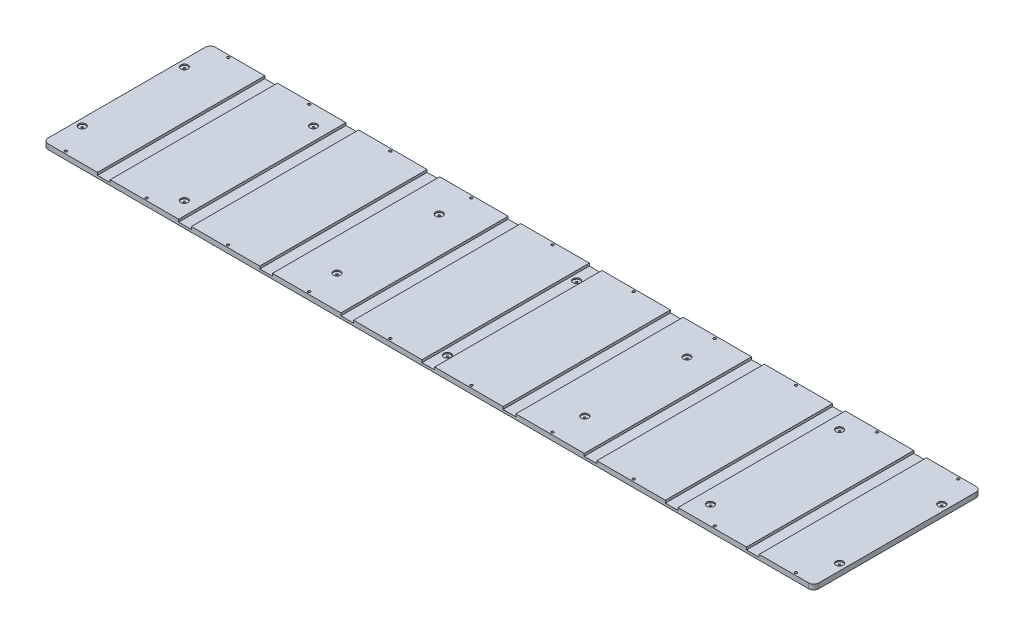
SolidWorks part; units mm, degrees
material "PE High Density"
ref_plane "Front Plane" through (0, 0, 0) normal (0, 0, 1) x (1, 0, 0)
ref_plane "Top Plane" through (0, 0, 0) normal (0, 1, 0) x (1, 0, 0)
ref_plane "Right Plane" through (0, 0, 0) normal (1, 0, 0) x (0, 0, -1)
sketch "Sketch1" plane through (0, 0, 0) normal (0, 1, 0) x (1, 0, 0)
  line L1 (0, 0) -> (1930.4, 0)
  line L2 (0, 0) -> (0, 419.1)
  line L3 (0, 419.1) -> (1930.4, 419.1)
  line L4 (1930.4, 0) -> (1930.4, 419.1)
  dimension "D1" = 1930.4
  dimension "D2" = 419.1
extrude "Boss-Extrude1" add sketch "Sketch1" along normal blind 12.7
sketch "Sketch2" plane through (0, 12.7, 0) normal (0, 1, 0) x (1, 0, 0)
  line L0 (1930.4, 419.1) -> (0, 419.1) construction
  line L2 (0, 419.1) -> (0, 0) construction
  line L3 (965.2, 419.1) -> (965.2, 0) construction
  line L4 (0, 0) -> (1930.4, 0) construction
  circle A0 centre (16.6688, 337.566) radius 2.4511
  circle A1 centre (654.8438, 337.566) radius 2.4511
  circle A2 centre (654.8438, 81.534) radius 2.4511
  circle A3 centre (16.6688, 81.534) radius 2.4511
  circle A4 centre (1275.5562, 337.566) radius 2.4511
  circle A5 centre (1275.5563, 81.534) radius 2.4511
  circle A6 centre (1913.7312, 337.566) radius 2.4511
  circle A7 centre (1913.7312, 81.534) radius 2.4511
  point P0 (16.6688, 337.566)
  point P5 (654.8438, 337.566)
  point P10 (654.8438, 81.534)
  point P17 (16.6688, 81.534)
  point P20 (1293.0187, 337.566)
  point P21 (1293.0187, 81.534)
  point P22 (1931.1937, 81.534)
  point P23 (1931.1937, 337.566)
  point P24 (1275.5562, 337.566)
  point P25 (1275.5563, 81.534)
  point P26 (1913.7312, 81.534)
  point P27 (1913.7312, 337.566)
  point P44 (0, 209.55)
  dimension "D7" = 4.9022
  dimension "D5" = 16.6687
  dimension "D6" = 256.032
  dimension "D4" = 638.175
  dimension "D1" = 128.016
  dimension "D2" = 4
  dimension "D3" = 2
sketch "Sketch7" plane through (0, 12.7, 0) normal (0, 1, 0) x (1, 0, 0)
  line L0 (0, 419.1) -> (0, 0) construction
  line L1 (0, 371.348) -> (1930.4, 371.348) construction
  line L2 (1930.4, 0) -> (1930.4, 419.1) construction
  circle A0 centre (306.324, 371.348) radius 2.4511
  circle A1 centre (306.324, 47.752) radius 2.4511
  circle A2 centre (965.2, 47.752) radius 2.4511
  circle A3 centre (965.2, 371.348) radius 2.4511
  circle A4 centre (1624.076, 371.348) radius 2.4511
  circle A5 centre (1624.076, 47.752) radius 2.4511
  point P0 (306.324, 371.348)
  point P3 (0, 209.55)
  point P8 (965.2, 371.348)
  point P9 (1624.076, 371.348)
  point P13 (965.2, 47.752)
  point P14 (1624.076, 47.752)
  point P18 (306.324, 47.752)
  dimension "D7" = 4.9022
  dimension "D5" = 658.876
  dimension "D6" = 323.596
  dimension "D2" = 161.798
  dimension "D3" = 3
fillet "Fillet1" radius 12.7 4 edges at (1930.4, 6.35, 0) (1930.4, 6.35, -419.1) (0, 6.35, 0) (0, 6.35, -419.1)
sketch "Sketch8" plane through (0, 12.7, 0) normal (0, 1, 0) x (1, 0, 0)
  line L0 (136.525, 419.1) -> (136.525, 0)
  line L1 (1917.7, 419.1) -> (12.7, 419.1) construction
  line L2 (12.7, 0) -> (1917.7, 0) construction
  line L3 (168.275, 419.1) -> (168.275, 0)
  line L4 (136.525, 419.1) -> (168.275, 419.1)
  line L5 (136.525, 0) -> (168.275, 0)
  line L6 (0, 406.4) -> (0, 12.7) construction
  line L7 (339.725, 0) -> (371.475, 0)
  line L8 (371.475, 419.1) -> (371.475, 0)
  line L9 (339.725, 419.1) -> (371.475, 419.1)
  line L10 (339.725, 419.1) -> (339.725, 0)
  line L11 (542.925, 0) -> (574.675, 0)
  line L12 (574.675, 419.1) -> (574.675, 0)
  line L13 (542.925, 419.1) -> (574.675, 419.1)
  line L14 (542.925, 419.1) -> (542.925, 0)
  line L15 (746.125, 0) -> (777.875, 0)
  line L16 (777.875, 419.1) -> (777.875, 0)
  line L17 (746.125, 419.1) -> (777.875, 419.1)
  line L18 (746.125, 419.1) -> (746.125, 0)
  line L19 (949.325, 0) -> (981.075, 0)
  line L20 (981.075, 419.1) -> (981.075, 0)
  line L21 (949.325, 419.1) -> (981.075, 419.1)
  line L22 (949.325, 419.1) -> (949.325, 0)
  line L23 (1152.525, 0) -> (1184.275, 0)
  line L24 (1184.275, 419.1) -> (1184.275, 0)
  line L25 (1152.525, 419.1) -> (1184.275, 419.1)
  line L26 (1152.525, 419.1) -> (1152.525, 0)
  line L27 (1355.725, 0) -> (1387.475, 0)
  line L28 (1387.475, 419.1) -> (1387.475, 0)
  line L29 (1355.725, 419.1) -> (1387.475, 419.1)
  line L30 (1355.725, 419.1) -> (1355.725, 0)
  line L31 (1558.925, 0) -> (1590.675, 0)
  line L32 (1590.675, 419.1) -> (1590.675, 0)
  line L33 (1558.925, 419.1) -> (1590.675, 419.1)
  line L34 (1558.925, 419.1) -> (1558.925, 0)
  line L35 (1762.125, 0) -> (1793.875, 0)
  line L36 (1793.875, 419.1) -> (1793.875, 0)
  line L37 (1762.125, 419.1) -> (1793.875, 419.1)
  line L38 (1762.125, 419.1) -> (1762.125, 0)
  dimension "D1" = 31.75
  dimension "D2" = 136.525
  dimension "D4" = 203.2
  dimension "D3" = 9
extrude "Cut-Extrude3" cut sketch "Sketch8" against normal blind 6.35
hole_wizard "1/4 (0.25) Diameter Hole1" positions "Sketch9" profile "Sketch10" hole size "1/4" standard "ANSI Inch" end condition through all
sketch "Sketch9" plane through (0, 12.7, 0) normal (0, 1, 0) x (1, 0, 0)
  line L1 (168.275, 0) -> (339.725, 0) construction
  line L2 (168.275, 0) -> (168.275, 419.1) construction
  line L3 (0, 209.55) -> (1930.4, 209.55) construction
  line L4 (0, 406.4) -> (0, 12.7) construction
  line L5 (1930.4, 12.7) -> (1930.4, 406.4) construction
  point P8 (254, 6.35)
  point P33 (457.2, 6.35)
  point P34 (660.4, 6.35)
  point P35 (863.6, 6.35)
  point P36 (1066.8, 6.35)
  point P37 (1270, 6.35)
  point P38 (1473.2, 6.35)
  point P39 (1676.4, 6.35)
  point P40 (254, 6.35)
  point P41 (457.2, 6.35)
  point P42 (660.4, 6.35)
  point P43 (863.6, 6.35)
  point P44 (1066.8, 6.35)
  point P45 (1270, 6.35)
  point P46 (1473.2, 6.35)
  point P47 (50.8, 6.35)
  point P48 (1879.6, 6.35)
  point P49 (1676.4, 6.35)
  point P50 (1676.4, 412.75)
  point P51 (1879.6, 412.75)
  point P52 (50.8, 412.75)
  point P53 (1473.2, 412.75)
  point P54 (1270, 412.75)
  point P55 (1066.8, 412.75)
  point P56 (863.6, 412.75)
  point P57 (660.4, 412.75)
  point P58 (457.2, 412.75)
  point P59 (254, 412.75)
  dimension "D1" = 6.35
  dimension "D2" = 85.725
  dimension "D5" = 203.2
  dimension "D3" = 9
  dimension "D4" = 2
sketch "Sketch10" plane through (254, 12.7, -6.35) normal (1, 0, 0) x (0, 0, 1)
  line L0 (0, 0) -> (0, 12.7)
  line L1 (0, 12.7) -> (3.175, 12.7)
  line L2 (3.175, 12.7) -> (3.175, 0)
  line L5 (3.175, 0) -> (0, 0)
  line L11 (0, -6.35) -> (0, 107.95) construction
  dimension "Thru Hole Dia." = 6.35
  dimension "Thru Hole Depth" = 12.7
hole_wizard "CBORE for #10 Socket Head Cap Screw1" positions "Sketch11" profile "Sketch12" counterbore size "#10" standard "ANSI Inch" end condition through all
sketch "Sketch11" plane through (0, 12.7, 0) normal (0, 1, 0) x (1, 0, 0)
  point P0 (16.6688, 337.566)
  point P3 (16.6688, 81.534)
  point P6 (306.324, 47.752)
  point P9 (306.324, 371.348)
  point P12 (654.8438, 337.566)
  point P15 (654.8438, 81.534)
  point P18 (965.2, 371.348)
  point P21 (965.2, 47.752)
  point P24 (1275.5563, 81.534)
  point P27 (1275.5562, 337.566)
  point P30 (1624.076, 371.348)
  point P33 (1624.076, 47.752)
  point P36 (1913.7312, 81.534)
  point P39 (1913.7312, 337.566)
sketch "Sketch12" plane through (16.6688, 12.7, -337.566) normal (1, 0, 0) x (0, 0, 1)
  line L0 (0, 0) -> (0, 12.7)
  line L1 (0, 12.7) -> (2.4511, 12.7)
  line L3 (2.4511, 12.7) -> (2.4511, 3.175)
  line L4 (2.4511, 3.175) -> (9.0488, 3.175)
  line L5 (9.0488, 3.175) -> (9.0488, 0)
  line L7 (9.0488, 0) -> (0, 0)
  line L11 (0, -6.35) -> (0, 107.95) construction
  dimension "Thru Hole Dia." = 4.9022
  dimension "Thru Hole Depth" = 12.7
  dimension "C'Bore Dia." = 18.0975
  dimension "C'Bore Depth" = 3.175
hole_wizard "CBORE for #10 Binding Head Machine Screw1" positions "Sketch13" profile "Sketch14" counterbore size "#10" standard "ANSI Inch" end condition through all
sketch "Sketch13" plane through (0, 6.35, 0) normal (0, 1, 0) x (1, 0, 0)
  circle A0 centre (965.2, 371.348) radius 2.4511 construction
  circle A1 centre (965.2, 47.752) radius 2.4511 construction
  point P0 (965.2, 371.348)
  point P3 (965.2, 47.752)
sketch "Sketch14" plane through (965.2, 6.35, -371.348) normal (1, 0, 0) x (0, 0, 1)
  line L0 (0, 0) -> (0, 6.35)
  line L1 (0, 6.35) -> (2.4511, 6.35)
  line L3 (2.4511, 6.35) -> (2.4511, 3.175)
  line L4 (2.4511, 3.175) -> (9.0488, 3.175)
  line L5 (9.0488, 3.175) -> (9.0488, 0)
  line L7 (9.0488, 0) -> (0, 0)
  line L11 (0, -6.35) -> (0, 107.95) construction
  dimension "Thru Hole Dia." = 4.9022
  dimension "Thru Hole Depth" = 6.35
  dimension "C'Bore Dia." = 18.0975
  dimension "C'Bore Depth" = 3.175
equation "\"D1@Sketch2\"=\"D6@Sketch2\"/2"
equation "\"D2@Sketch7\"=\"D6@Sketch7\"/2"
